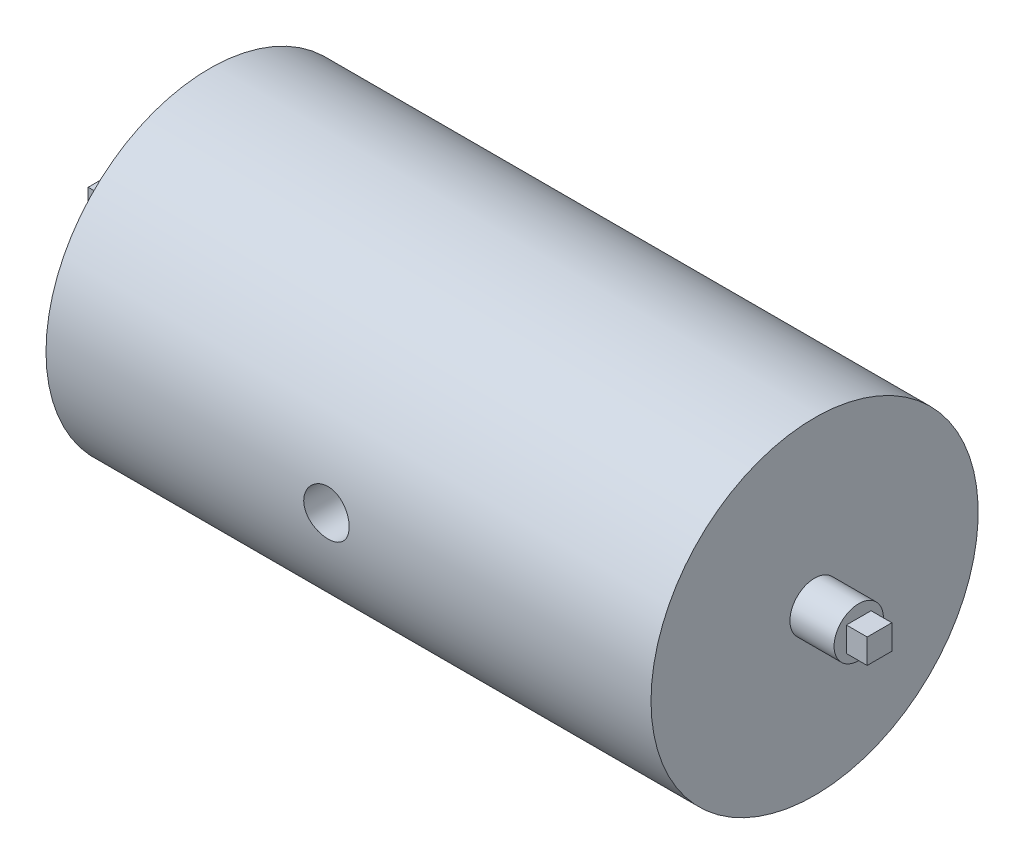
SolidWorks part; units mm, degrees
ref_plane "Plan de face" through (0, 0, 0) normal (0, 0, 1) x (1, 0, 0)
ref_plane "Plan de dessus" through (0, 0, 0) normal (0, 1, 0) x (1, 0, 0)
ref_plane "Plan de droite" through (0, 0, 0) normal (1, 0, 0) x (0, 0, -1)
sketch "Esquisse1" plane through (0, 0, 0) normal (0, 1, 0) x (1, 0, 0)
  line L0 (0, 0) -> (0, 4.75)
  line L1 (0, 4.75) -> (142, 4.75)
  line L2 (142, 4.75) -> (142, 0)
  line L30 (133.5, 0) -> (133.5, -26.75)
  line L35 (17, -26.75) -> (17, 0)
  line L36 (142, 0) -> (133.5, 0)
  line L38 (17, 0) -> (0, 0)
  line L39 (133.5, -26.75) -> (17, -26.75)
  dimension "D1" = 142
  dimension "D2" = 8.5
  dimension "D3" = 17
  dimension "D4" = 31.5
  dimension "D5" = 4.75
  dimension "D8" = 4.75
revolve "Révolution1" add sketch "Esquisse1" angle 360 about L1
sketch "Esquisse5" plane through (142, 0, 0) normal (1, 0, 0) x (0, 0, -1)
  line L0 (2.375, 2.375) -> (2.375, -2.375)
  line L9 (2.375, 2.375) -> (7.125, 2.375)
  line L10 (7.125, 2.375) -> (7.125, -2.375)
  line L11 (7.125, -2.375) -> (2.375, -2.375)
extrude "Boss.-Extru.3" add sketch "Esquisse5" along normal blind 4
sketch "Esquisse6" plane through (0, 0, 0) normal (-1, 0, 0) x (0, 0, 1)
  line L8 (-4.75, 2.375) -> (-7.125, 2.375)
  line L9 (-7.125, 2.375) -> (-7.125, -2.375)
  line L10 (-7.125, -2.375) -> (-2.375, -2.375)
  line L11 (-2.375, -2.375) -> (-2.375, 2.375)
  line L12 (-2.375, 2.375) -> (-4.75, 2.375)
extrude "Boss.-Extru.4" add sketch "Esquisse6" along normal blind 4
sketch3d "Esquisse3D1"
  line L0 (0, 0, 0) -> (142, 0, 0) construction
  circle A1 centre (71, 0, 0) radius 1.5
  point P5 (71, 0, 1.5)
  dimension "D2" = 3
  dimension "D1" = 142
sketch "Esquisse10" plane through (0, 0, 0) normal (0, 0, 1) x (1, 0, 0)
  line L1 (63.31, 0) -> (67.155, -6.6597)
  line L2 (67.155, -6.6597) -> (74.845, -6.6597)
  line L3 (74.845, -6.6597) -> (78.69, 0)
  line L4 (78.69, 0) -> (74.845, 6.6597)
  line L5 (74.845, 6.6597) -> (67.155, 6.6597)
  line L6 (67.155, 6.6597) -> (63.31, 0)
  circle A1 centre (71, 0) radius 4.375
  dimension "D3" = 8.75
  dimension "D1" = 15.38
  dimension "D2" = 13.3195
extrude "Enlèv. mat.-Extru.2" cut sketch "Esquisse10" against normal blind 50
sketch "Esquisse11" plane through (0, 0, 0) normal (0, 0, 1) x (1, 0, 0)
  circle A0 centre (71, 0) radius 4.375
  dimension "D1" = 8.75
extrude "Enlèv. mat.-Extru.3" cut sketch "Esquisse11" against normal blind 50 and the other way blind 50
